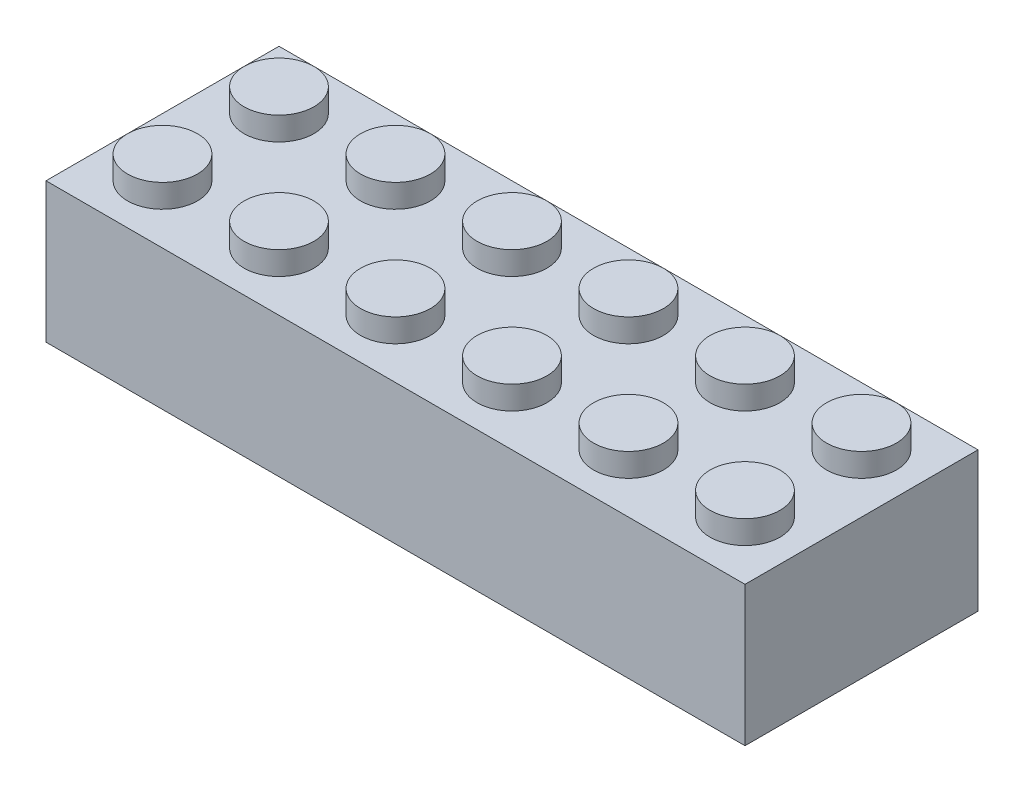
SolidWorks part; units mm, degrees
ref_plane "Front Plane" through (0, 0, 0) normal (0, 0, 1) x (1, 0, 0)
ref_plane "Top Plane" through (0, 0, 0) normal (0, 1, 0) x (1, 0, 0)
ref_plane "Right Plane" through (0, 0, 0) normal (1, 0, 0) x (0, 0, -1)
sketch "Sketch1" plane through (0, 0, 0) normal (0, 1, 0) x (1, 0, 0)
  line L1 (-15, -5) -> (15, -5)
  line L2 (-15, -5) -> (-15, 5)
  line L3 (-15, 5) -> (15, 5)
  line L4 (15, -5) -> (15, 5)
  line L5 (-15, -5) -> (15, 5) construction
  line L6 (-15, 5) -> (15, -5) construction
  line L7 (-14, 4) -> (14, 4)
  line L8 (-14, 4) -> (-14, -4)
  line L9 (-14, -4) -> (14, -4)
  line L10 (14, 4) -> (14, -4)
  line L11 (-14, 4) -> (14, -4) construction
  line L12 (-14, -4) -> (14, 4) construction
  circle A0 centre (-12.5, 2.5) radius 1.5
  circle A1 centre (-7.5, 2.5) radius 1.5
  circle A2 centre (-2.5, 2.5) radius 1.5
  circle A3 centre (2.5, 2.5) radius 1.5
  circle A4 centre (7.5, 2.5) radius 1.5
  circle A5 centre (12.5, 2.5) radius 1.5
  circle A6 centre (-7.5, -2.5) radius 1.5
  circle A7 centre (-2.5, -2.5) radius 1.5
  circle A8 centre (2.5, -2.5) radius 1.5
  circle A9 centre (7.5, -2.5) radius 1.5
  circle A10 centre (12.5, -2.5) radius 1.5
  circle A11 centre (-12.5, -2.5) radius 1.5
  circle A12 centre (-10, 0) radius 2.0355
  circle A13 centre (-5, 0) radius 2.0355
  circle A14 centre (0, 0) radius 2.0355
  circle A15 centre (5, 0) radius 2.0355
  circle A16 centre (10, 0) radius 2.0355
  circle A17 centre (-10, 0) radius 1.5
  circle A18 centre (-5, 0) radius 1.5
  circle A19 centre (0, 0) radius 1.5
  circle A20 centre (5, 0) radius 1.5
  circle A21 centre (10, 0) radius 1.5
  point P0 (0, 0)
  dimension "D5" = 3
  dimension "D11" = 3
  dimension "D1" = 10
  dimension "D2" = 30
  dimension "D3" = 2.5
  dimension "D4" = 2.5
  dimension "D9" = 1
  dimension "D10" = 1
  dimension "D6" = 6
  dimension "D7" = 2
  dimension "D8" = 5
  dimension "D12" = 5
extrude "Boss-Extrude1" add sketch "Sketch1" along normal blind 2 contours A2 | A1 | A0 | A11 | A6 | A7 | A3 | A4 | A5 | A10 | A9 | A8 region at (-12.5, 0, -2.5) region at (-7.5, 0, -2.5) region at (-12.5, 0, 2.5) region at (-2.5, 0, -2.5) region at (2.5, 0, -2.5) region at (-7.5, 0, 2.5) region at (7.5, 0, -2.5) region at (-2.5, 0, 2.5) region at (12.5, 0, -2.5) region at (2.5, 0, 2.5) region at (7.5, 0, 2.5) region at (12.5, 0, 2.5)
extrude "Boss-Extrude2" add sketch "Sketch1<3>" along normal blind 1 contours L2 L3 L4 L1
sketch "Sketch1<3>" plane through (0, 0, 0) normal (0, 1, 0) x (1, 0, 0) same geometry as "Sketch1"
extrude "Boss-Extrude3" add sketch "Sketch1<4>" against normal blind 5 contours L1 L4 L3 L2 L7 L10 L9 L8 | A12 A17 | A13 A18 | A14 A19 | A15 A20 | A16 A21 region at (-14.6838, 0, 0) region at (-10, 0, -1.978) region at (-3.1726, 0, -0.7569) region at (1.8274, 0, -0.7569) region at (6.8274, 0, -0.7569) region at (11.8274, 0, -0.7569)
sketch "Sketch1<4>" plane through (0, 0, 0) normal (0, 1, 0) x (1, 0, 0) same geometry as "Sketch1"
